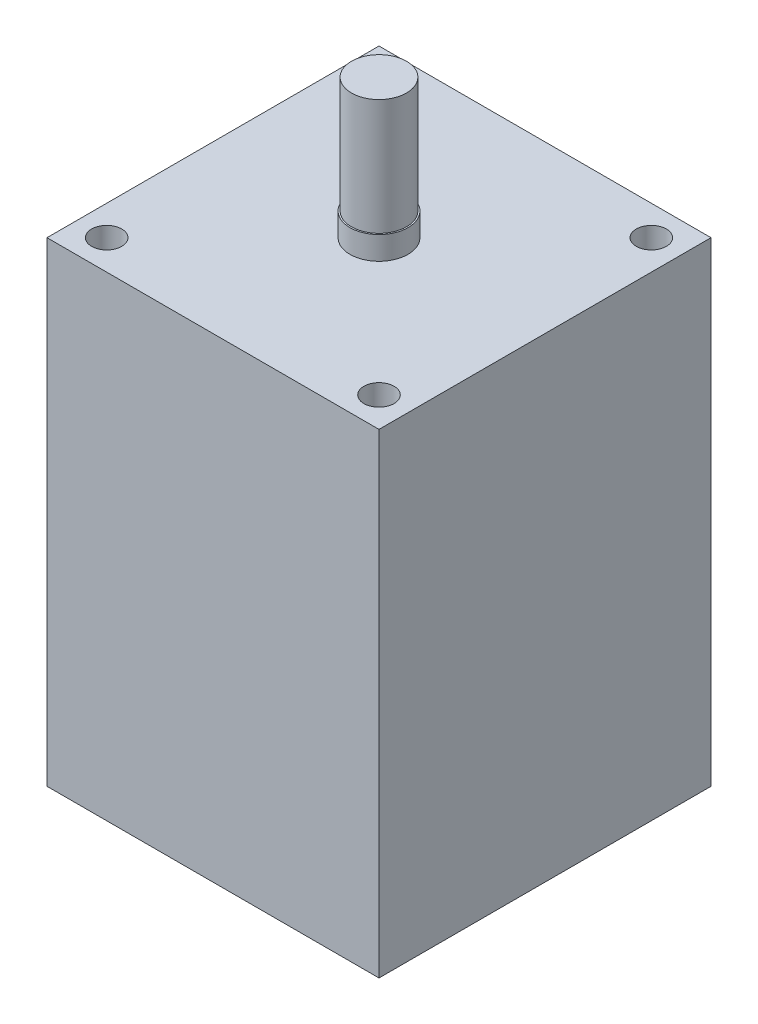
SolidWorks part; units mm, degrees
ref_plane "Front Plane" through (0, 0, 0) normal (0, 0, 1) x (1, 0, 0)
ref_plane "Top Plane" through (0, 0, 0) normal (0, 1, 0) x (1, 0, 0)
ref_plane "Right Plane" through (0, 0, 0) normal (1, 0, 0) x (0, 0, -1)
sketch "Sketch1" plane through (0, 0, 0) normal (0, 1, 0) x (1, 0, 0)
  line L1 (0, 0) -> (57.3, 0)
  line L2 (0, 0) -> (0, -57.3)
  line L3 (0, -57.3) -> (57.3, -57.3)
  line L4 (57.3, 0) -> (57.3, -57.3)
  circle A0 centre (5.15, -5.15) radius 2.6
  circle A1 centre (52.15, -5.15) radius 2.6
  circle A2 centre (5.15, -52.15) radius 2.6
  circle A3 centre (52.15, -52.15) radius 2.6
  circle A4 centre (28.65, -28.65) radius 5
  circle A5 centre (28.65, -28.65) radius 4.75
  dimension "D5" = 5.2
  dimension "D6" = 10
  dimension "D7" = 9.5
  dimension "D1" = 57.3
  dimension "D2" = 57.3
  dimension "D3" = 47
  dimension "D4" = 47
  dimension "D8" = 28.65
  dimension "D9" = 28.65
  dimension "D10" = 5.15
  dimension "D11" = 5.15
extrude "Boss-Extrude1" add sketch "Sketch1" along normal blind 82 contours L4 L1 L2 L3 A4 A3 A2 A1 A0 region at (28.65, 0, 0.8103)
extrude "Boss-Extrude2" add sketch "Sketch1<4>" along normal blind 4 from surface contours A4 A5 region at (23.7914, 0, 28.65) starting at face at (28.65, 82, 33.65)
sketch "Sketch1<4>" plane through (0, 0, 0) normal (0, 1, 0) x (1, 0, 0) same geometry as "Sketch1"
extrude "Boss-Extrude3" add sketch "Sketch1<5>" along normal blind 24 from surface contours A5 region at (28.65, 0, 28.65) starting at face at (28.65, 82, 33.65)
sketch "Sketch1<5>" plane through (0, 0, 0) normal (0, 1, 0) x (1, 0, 0) same geometry as "Sketch1"
equation "\"D8@Sketch1\"=\"D1@Sketch1\"/2"
equation "\"D9@Sketch1\"=\"D2@Sketch1\"/2"
equation "\"D10@Sketch1\"=(\"D1@Sketch1\"-\"D3@Sketch1\")/2"
equation "\"D11@Sketch1\"=(\"D1@Sketch1\"-\"D3@Sketch1\")/2"
